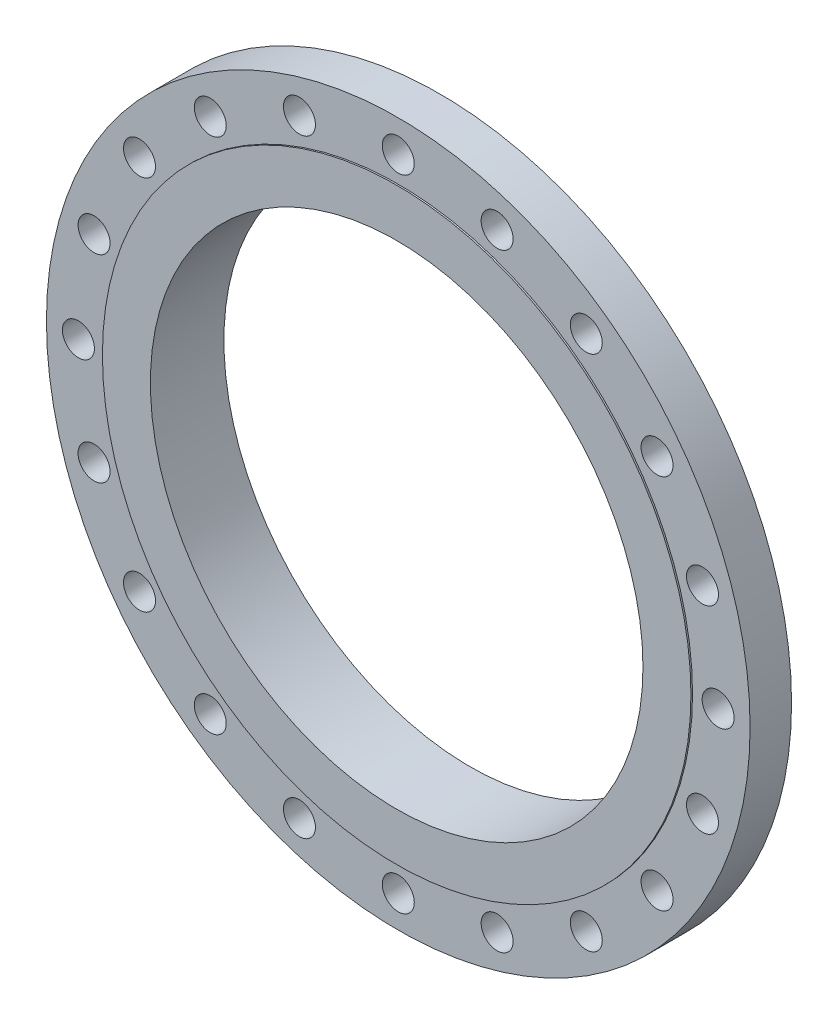
SolidWorks part; units mm, degrees
ref_plane "Front Plane" through (0, 0, 0) normal (0, 0, 1) x (1, 0, 0)
ref_plane "Top Plane" through (0, 0, 0) normal (0, 1, 0) x (1, 0, 0)
ref_plane "Right Plane" through (0, 0, 0) normal (1, 0, 0) x (0, 0, -1)
sketch "Sketch1" plane through (0, 0, 0) normal (0, 0, 1) x (1, 0, 0)
  circle A0 centre (0, 0) radius 9.625
  circle A1 centre (0, 0) radius 13.75
  circle A2 centre (0, 0) radius 11.5
  point P48 (0, 0)
  dimension "D18" = 19.25
  dimension "D19" = 23
  dimension "D20" = 27.5
extrude "Boss-Extrude1" add sketch "Sketch1" along normal blind 1.6825 contours A2
extrude "Cut-Extrude1" cut sketch "Sketch1<5>" along normal blind 3.6825 contours A0
sketch "Sketch1<5>" plane through (0, 0, 0) normal (0, 0, 1) x (1, 0, 0) same geometry as "Sketch1"
extrude "Boss-Extrude2" add sketch "Sketch1<6>" along normal blind 1.62 contours A1
sketch "Sketch1<6>" plane through (0, 0, 0) normal (0, 0, 1) x (1, 0, 0) same geometry as "Sketch1"
extrude "Cut-Extrude2" cut sketch "Sketch1<7>" along normal blind 14.62 contours A0
sketch "Sketch1<7>" plane through (0, 0, 0) normal (0, 0, 1) x (1, 0, 0) same geometry as "Sketch1"
sketch "Sketch7" plane through (0, 0, 0) normal (0, 0, 1) x (1, 0, 0)
  circle A0 centre (0, 12.5) radius 0.625
  circle A1 centre (3.8627, 11.8882) radius 0.625
  circle A2 centre (7.3473, 10.1127) radius 0.625
  circle A3 centre (10.1127, 7.3473) radius 0.625
  circle A4 centre (11.8882, 3.8627) radius 0.625
  circle A5 centre (12.5, 0) radius 0.625
  circle A6 centre (11.8882, -3.8627) radius 0.625
  circle A7 centre (10.1127, -7.3473) radius 0.625
  circle A8 centre (7.3473, -10.1127) radius 0.625
  circle A9 centre (3.8627, -11.8882) radius 0.625
  circle A10 centre (0, -12.5) radius 0.625
  circle A11 centre (-3.8627, -11.8882) radius 0.625
  circle A12 centre (-7.3473, -10.1127) radius 0.625
  circle A13 centre (-10.1127, -7.3473) radius 0.625
  circle A14 centre (-11.8882, -3.8627) radius 0.625
  circle A15 centre (-12.5, 0) radius 0.625
  circle A16 centre (-11.8882, 3.8627) radius 0.625
  circle A17 centre (-10.1127, 7.3473) radius 0.625
  circle A18 centre (-7.3473, 10.1127) radius 0.625
  circle A19 centre (-3.8627, 11.8882) radius 0.625
  circle A20 centre (0, 0) radius 11
  point P43 (0, 0)
  dimension "D1" = 20
  dimension "D3" = 22
  dimension "D2" = 1.25
extrude "Cut-Extrude5" cut sketch "Sketch7" along normal blind 58.62 contours A0
sketch "Sketch9" plane through (0, 0, 0) normal (0, 1, 0) x (1, 0, 0)
  line L0 (0, 0) -> (0, -5.4885) construction
pattern_circular "CirPattern1" count 20 over 360 about axis through (0, 0, 0) along (0, 0, 1) of "Cut-Extrude5" reverse direction yes
extrude "Boss-Extrude3" add sketch "Sketch1<8>" against normal blind 1.19 contours A2
sketch "Sketch1<8>" plane through (0, 0, 0) normal (0, 0, 1) x (1, 0, 0) same geometry as "Sketch1"
extrude "Cut-Extrude6" cut sketch "Sketch1<9>" against normal blind 19.19 contours A0
sketch "Sketch1<9>" plane through (0, 0, 0) normal (0, 0, 1) x (1, 0, 0) same geometry as "Sketch1"
scale "Scale1" scale about centroid uniform scaling yes scale factor 25.4
